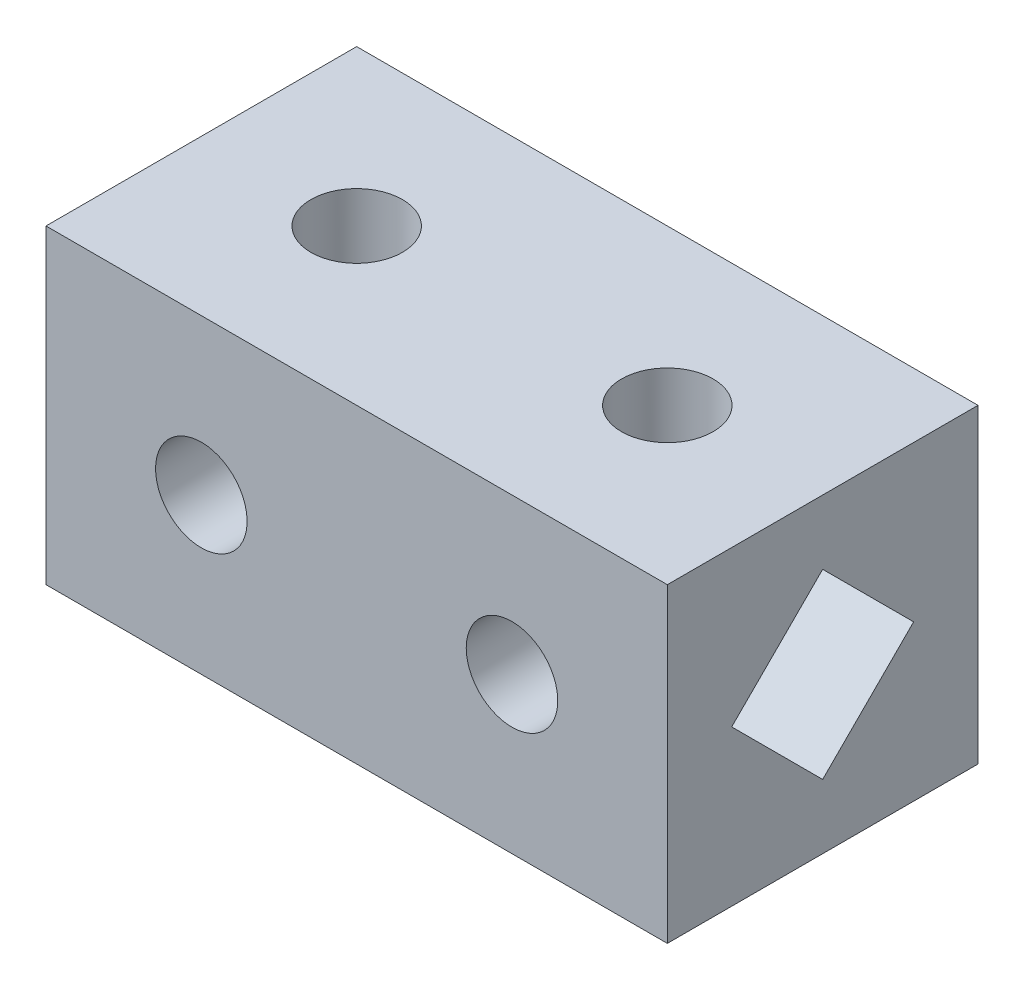
SolidWorks part; units mm, degrees
ref_plane "Front Plane" through (0, 0, 0) normal (0, 0, 1) x (1, 0, 0)
ref_plane "Top Plane" through (0, 0, 0) normal (0, 1, 0) x (1, 0, 0)
ref_plane "Right Plane" through (0, 0, 0) normal (1, 0, 0) x (0, 0, -1)
other "Configuration Table"
sketch "sketch1" plane through (0, 0, 0) normal (0, 1, 0) x (1, 0, 0)
  line L0 (0, -8.5) -> (8.5, -8.5) construction
  line L1 (0, 0) -> (34, 0)
  line L2 (0, 0) -> (0, -17)
  line L3 (0, -17) -> (34, -17)
  line L4 (34, 0) -> (34, -17)
  line L5 (8.5, -8.5) -> (25.5, -8.5) construction
  circle A1 centre (8.5, -8.5) radius 2.505
  circle A2 centre (25.5, -8.5) radius 2.505
  dimension "D4" = 5.01
  dimension "D1" = 17
  dimension "D2" = 34
  dimension "D3" = 8.5
  dimension "D6" = 17
extrude "Boss-Extrude1" add sketch "sketch1" along normal blind 17
sketch "Sketch6" plane through (0, 0, 0) normal (0, 0, -1) x (-1, 0, 0)
  line L0 (-34, 8.5) -> (-25.5, 8.5) construction
  line L1 (-25.5, 8.5) -> (-8.5, 8.5) construction
  line L4 (-34, 0) -> (0, 0)
  line L5 (0, 0) -> (0, 17)
  line L6 (0, 17) -> (-34, 17)
  line L7 (-34, 17) -> (-34, 0)
  line L8 (-34, 0) -> (0, 0)
  line L9 (0, 0) -> (0, 17)
  line L10 (0, 17) -> (-34, 17)
  line L11 (-34, 17) -> (-34, 0)
  circle A0 centre (-25.5, 8.5) radius 2.505
  circle A1 centre (-8.5, 8.5) radius 2.505
  dimension "D3" = 5.01
  dimension "D2" = 8.5
  dimension "D5" = 17
  dimension "D4" = 2
extrude "Cut-Extrude10" cut sketch "Sketch6" against normal through all flip side to cut
sketch "Sketch7" plane through (34, 0, 0) normal (1, 0, 0) x (0, 0, -1)
  line L0 (-17, 8.5) -> (0, 8.5) construction
  line L1 (-8.5, 8.5) -> (-8.5, 13.478) construction
  line L2 (-8.5, 13.478) -> (-3.522, 8.5)
  line L3 (-3.522, 8.5) -> (-8.5, 3.522)
  line L4 (-17, 0) -> (0, 0)
  line L5 (0, 0) -> (0, 17)
  line L6 (0, 17) -> (-17, 17)
  line L7 (-17, 17) -> (-17, 0)
  line L8 (-17, 0) -> (0, 0)
  line L9 (0, 0) -> (0, 17)
  line L10 (0, 17) -> (-17, 17)
  line L11 (-17, 17) -> (-17, 0)
  line L12 (-8.5, 3.522) -> (-13.478, 8.5)
  line L13 (-13.478, 8.5) -> (-8.5, 13.478)
  dimension "D2" = 7.04
extrude "Cut-Extrude11" cut sketch "Sketch7" against normal blind 34 flip side to cut
equation "\"D2@sketch1\" = \"length\""
equation "\"holes\"= 2"
equation "\"cdist\"= 17mm'centre distance between holes"
equation "\"width\"= 17mm"
equation "\"length\"= \"cdist\" * \"holes\""
equation "\"D1@sketch1\" = \"width\""
equation "\"hdiam\"= 5.01mm'Hole diametre"
equation "\"D4@sketch1\" = \"hdiam\""
equation "\"D6@sketch1\" = \"cdist\""
equation "\"D5@sketch1\" = \"holes\""
equation "\"D2@Sketch6\"=\"cdist\"/2"
equation "\"D3@Sketch6\"=\"hdiam\""
equation "\"D5@Sketch6\"=\"cdist\""
equation "\"D4@Sketch6\"=\"holes\""
equation "\"D1@Boss-Extrude1\"=\"width\""
equation "\"insetwidth\"= 7mm"
equation "\"tolerance\"= 0.04mm"
equation "\"D2@Sketch7\"=\"insetwidth\"+\"tolerance\""
equation "\"D1@Cut-Extrude11\"=\"length\""
